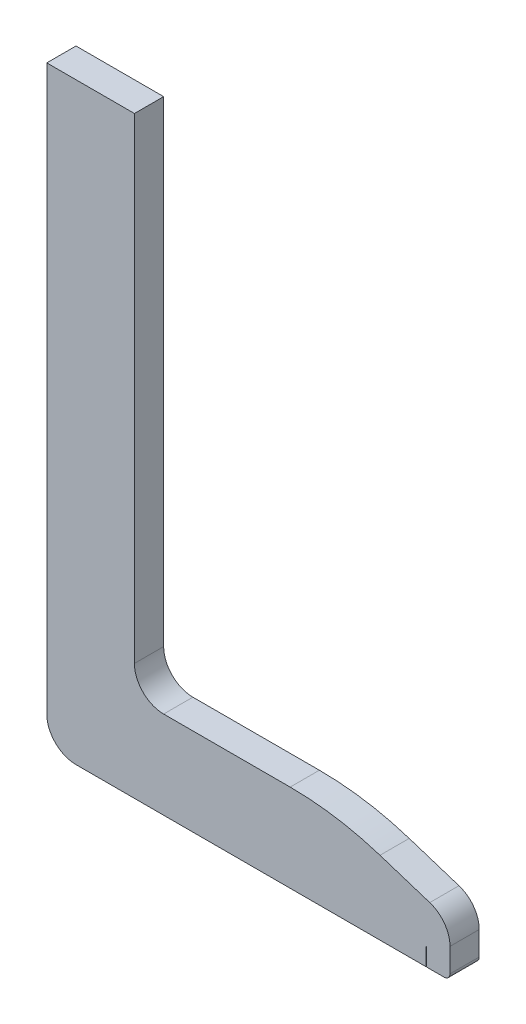
SolidWorks part; units mm, degrees
ref_plane "Front Plane" through (0, 0, 0) normal (0, 0, 1) x (1, 0, 0)
ref_plane "Top Plane" through (0, 0, 0) normal (0, 1, 0) x (1, 0, 0)
ref_plane "Right Plane" through (0, 0, 0) normal (1, 0, 0) x (0, 0, -1)
sketch "Sketch1" plane through (0, 0, 0) normal (0, 0, 1) x (1, 0, 0)
  line L0 (0, -1) -> (0, -96.5)
  line L1 (5, -101.5) -> (68, -101.5)
  line L2 (69, -100.5) -> (69, -96.43)
  line L3 (41.65, -86.5) -> (20, -86.5)
  line L4 (15, -81.5) -> (15, -1)
  line L5 (14, 0) -> (1, 0)
  line L6 (15, -1) -> (15, 0)
  line L7 (15, 0) -> (14, 0)
  line L8 (0, -1) -> (0, 0)
  line L9 (0, 0) -> (1, 0)
  line L10 (65.5369, -91.6721) -> (57.0187, -88.9206)
  arc A2 (69, -100.5) -> (68, -101.5) centre (68, -100.5) cw
  arc A4 (5, -101.5) -> (0, -96.5) centre (5, -96.5) cw
  arc A5 (15, -81.5) -> (20, -86.5) centre (20, -81.5) ccw
  arc A6 (65.5369, -91.6721) -> (69, -96.43) centre (64, -96.43) cw
  arc A7 (41.65, -86.5) -> (57.0187, -88.9206) centre (41.65, -136.5) cw
  point P9 (0, 0)
  point P12 (15, 0)
  point P15 (69, -101.5)
  point P18 (69, -86.5)
  point P21 (0, -101.5)
  point P24 (15, -86.5)
  dimension "D6" = 5
  dimension "D5" = 5
  dimension "D7" = 50
  dimension "D1" = 86.5
  dimension "D2" = 15
  dimension "D3" = 69
  dimension "D4" = 15
extrude "Boss-Extrude1" add sketch "Sketch1" along normal blind 5
sketch "Sketch2" plane through (0, -101.5, 0) normal (0, -1, 0) x (1, 0, 0)
  line L0 (0, 2.5) -> (64.9, 2.5) construction
  line L1 (0, 5) -> (0, 0) construction
  line L2 (5, 5) -> (68, 5) construction
  line L3 (64.85, 0) -> (64.95, 0)
  line L4 (64.85, 0) -> (64.85, 5)
  line L5 (64.85, 5) -> (64.95, 5)
  line L6 (64.95, 0) -> (64.95, 5)
  line L7 (64.85, 0) -> (64.95, 5) construction
  line L8 (64.85, 5) -> (64.95, 0) construction
  dimension "D1" = 64.9
  dimension "D2" = 0.1
extrude "Cut-Extrude2" cut sketch "Sketch2" against normal blind 3
equation "\"A.L\"= 0.07m"
equation "\"A.h\"= 0.007m"
equation "\"A.d\"= 0.005m"
equation "\"A.delta\"= 45.0001"
equation "\"A.w\"= 0m"
equation "\"A.v\"= 0.013m"
equation "\"A.s\"= 0.014m"
equation "\"A.t\"= 0.007m"
equation "\"B.L\"= 0.065m"
equation "\"B.h\"= 0.008m"
equation "\"B.s\"= 0.016m"
equation "\"B.t\"= 0.008m"
equation "\"C.h\"= 0.0065m"
equation "\"C.d\"= 0.005m"
equation "\"C.L\"= 0.05m"
equation "\"C.wmax\"= 0.003m"
equation "\"D.L\"= 0.06m"
equation "\"D.h\"= 0.008m"
equation "\"D.s\"= 0.012m"
equation "\"D.t\"= 0.008m"
equation "\"a_h\"= 0.0001m"
equation "\"a_d\"= 0.005m"
equation "\"a_L\"= 0.008m"
equation "\"b_h\"= 0.0004m"
equation "\"b_d\"= 0.005m"
equation "\"b_L\"= 0.007m"
equation "\"c_h\"= 0.0001m"
equation "\"c_d\"= 0.005m"
equation "\"c_L\"= 0.01m"
equation "\"d_h\"= 0.0001m"
equation "\"d_d\"= 0.005m"
equation "\"d_L\"= 0.01m"
equation "\"S.h\"= 0.015m"
equation "\"S.L\"= 0.09275m"
equation "\"D1@Sketch1\"=\"S.L\"-\"C.wmax\"-\"C.h\"/2"
equation "\"D2@Sketch1\"=\"S.h\""
equation "\"D3@Sketch1\"=\"C.L\"+\"S.h\"+0.004"
equation "\"D4@Sketch1\"=\"S.h\""
equation "\"D1@Boss-Extrude1\"=0.005m"
equation "\"D1@Sketch2\"=\"C.L\"+\"S.h\"-\"d_h\""
equation "\"D2@Sketch2\"=\"d_h\""
